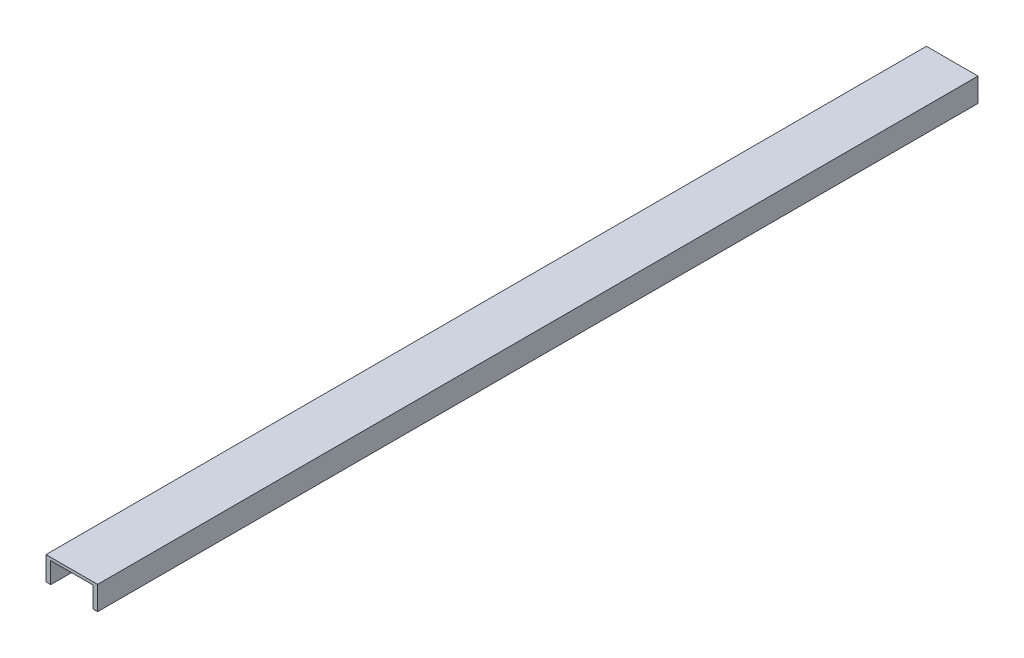
SolidWorks part; units mm, degrees
material "AISI 4340 Acero normalizado"
ref_plane "Alzado" through (0, 0, 0) normal (0, 0, 1) x (1, 0, 0)
ref_plane "Planta" through (0, 0, 0) normal (0, 1, 0) x (1, 0, 0)
ref_plane "Vista lateral" through (0, 0, 0) normal (1, 0, 0) x (0, 0, -1)
sketch "Croquis2" plane through (0, 0, 0) normal (0, 0, 1) x (1, 0, 0)
  line L0 (31.1, -17.5) -> (31.1, 13.2)
  line L1 (38.1, -17.5) -> (-38.1, -17.5)
  line L2 (38.1, -17.5) -> (38.1, 17.5)
  line L3 (38.1, 17.5) -> (-38.1, 17.5)
  line L4 (-38.1, -17.5) -> (-38.1, 17.5)
  line L5 (38.1, -17.5) -> (-38.1, 17.5) construction
  line L6 (38.1, 17.5) -> (-38.1, -17.5) construction
  line L7 (31.1, 13.2) -> (-31.1, 13.2)
  line L8 (-31.1, -17.5) -> (-31.1, 13.2)
  line L11 (31.1, -17.5) -> (-31.1, -17.5)
  point P0 (0, 0)
  point P10 (0, 0)
  point P12 (0, 0)
  dimension "D1" = 35
  dimension "D2" = 76.2
  dimension "D3" = 4.3
  dimension "D4" = 7
  dimension "D5" = 7
extrude "Saliente-Extruir1" add sketch "Croquis2" along normal mid plane 1300 contours L1 L8 L7 L0 L2 L3 L4 region at (31.9385, -2.15, 0)
